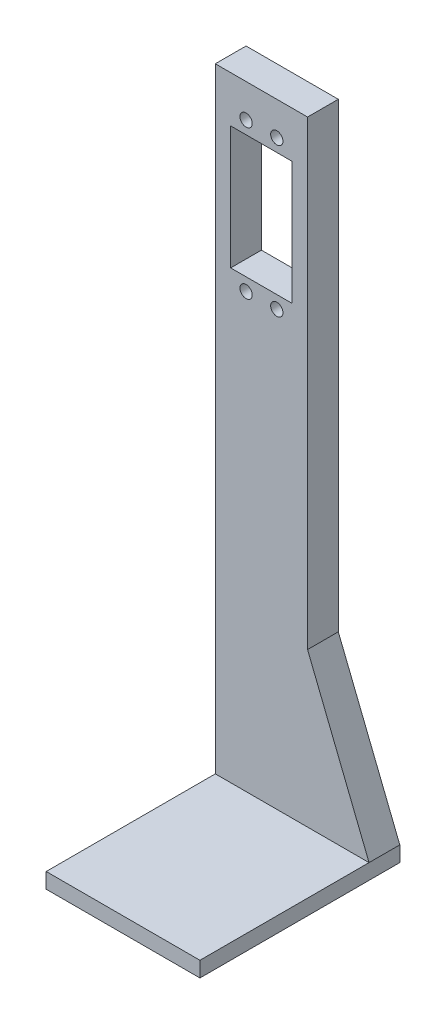
SolidWorks part; units mm, degrees
ref_plane "Front Plane" through (0, 0, 0) normal (0, 0, 1) x (1, 0, 0)
ref_plane "Top Plane" through (0, 0, 0) normal (0, 1, 0) x (1, 0, 0)
ref_plane "Right Plane" through (0, 0, 0) normal (1, 0, 0) x (0, 0, -1)
sketch "Sketch1" plane through (0, 0, 0) normal (0, 1, 0) x (1, 0, 0)
  line L0 (-50, 0) -> (-50, -65)
  line L1 (0, 0) -> (-50, 0)
  line L2 (0, 0) -> (0, -65)
  line L3 (0, -65) -> (-50, -65)
  dimension "D1" = 65
  dimension "D2" = 50
extrude "Boss-Extrude1" add sketch "Sketch1" along normal blind 5
sketch "Sketch2" plane through (0, 0, 0) normal (0, 0, 1) x (1, 0, 0)
  line L0 (0, 5) -> (-20, 55)
  line L1 (-20, 55) -> (-20, 205)
  line L2 (-20, 205) -> (-50, 205)
  line L3 (0, 5) -> (-50, 5)
  line L4 (-50, 5) -> (-50, 205)
  line L5 (0, 5) -> (-50, 5)
  dimension "D1" = 200
  dimension "D2" = 150
  dimension "D3" = 30
  dimension "D4" = 50
extrude "Boss-Extrude2" add sketch "Sketch2" along normal blind 10 contours L2 L4 L3 L0 L1
sketch "Sketch3" plane through (0, 0, 10) normal (0, 0, 1) x (1, 0, 0)
  line L0 (-50, 5) -> (-50, 205) construction
  line L1 (-45, 190) -> (-25, 190)
  line L2 (-45, 190) -> (-45, 150)
  line L3 (-45, 150) -> (-25, 150)
  line L4 (-25, 190) -> (-25, 150)
  line L5 (-20, 205) -> (-50, 205) construction
  circle A0 centre (-40, 194.15) radius 2
  circle A1 centre (-30, 194.15) radius 2
  circle A2 centre (-40, 145.85) radius 2
  circle A3 centre (-30, 145.85) radius 2
  dimension "D1" = 20
  dimension "D2" = 40
  dimension "D3" = 5
  dimension "D4" = 15
extrude "Cut-Extrude1" cut sketch "Sketch3" against normal through all
